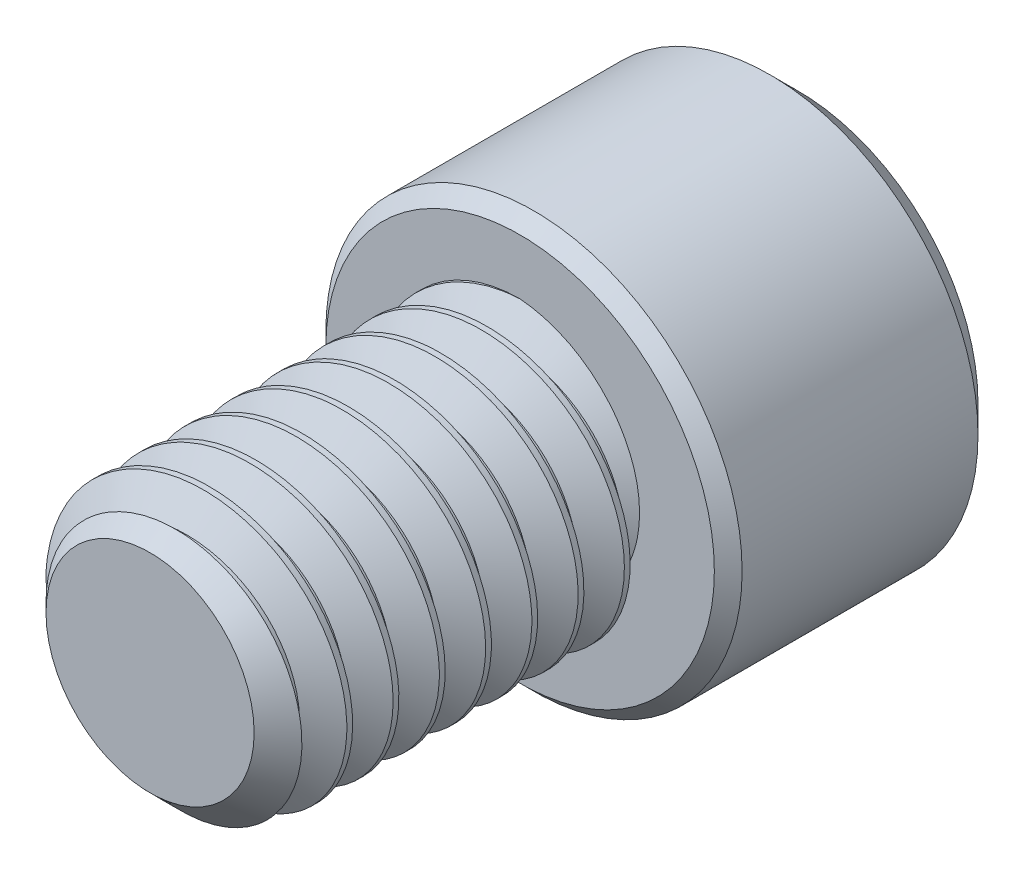
SolidWorks part; units mm, degrees
ref_plane "Front Plane" through (0, 0, 0) normal (0, 0, 1) x (1, 0, 0)
ref_plane "Top Plane" through (0, 0, 0) normal (0, 1, 0) x (1, 0, 0)
ref_plane "Right Plane" through (0, 0, 0) normal (1, 0, 0) x (0, 0, -1)
sketch "Sketch1" plane through (0, 0, 0) normal (0, 0, 1) x (1, 0, 0)
  line L0 (0, 4.7625) -> (0, -4.7625) construction
  circle A0 centre (0, 0) radius 4.7625
  dimension "OD" = 9.525
extrude "Extrude1" add sketch "Sketch1" against normal blind 12.7
sketch "Sketch2" plane through (0, 0, 0) normal (0, 0, 1) x (1, 0, 0)
  circle A0 centre (0, 0) radius 4.7625 construction
  circle A1 centre (0, 0) radius 4.7625
curve "Helix/Spiral1" pitch 1.5875 height 14.2875 turns 9 parameters "pitch"=1.5875
chamfer "Chamfer3" distance 1.1906 angle 45 1 edges at (4.7625, 0, 0)
sketch "Sketch3" plane through (0, 0, 0) normal (1, 0, 0) x (0, 0, -1)
  line L0 (-1.3891, 4.7625) -> (-0.7938, 3.7314)
  line L1 (-0.7938, 3.7314) -> (-0.5953, 3.7314)
  line L2 (-0.5953, 3.7314) -> (0, 4.7625)
  line L3 (-1.3891, 4.7625) -> (0, 4.7625)
  line L4 (-0.6945, 4.7625) -> (-0.6945, 3.7314) construction
  line L5 (-1.0914, 4.2469) -> (-0.2977, 4.2469) construction
  line L6 (0, 4.7625) -> (0, -4.7625) construction
  dimension "D1" = 0.1984
  dimension "D2" = 0.7937
  dimension "D3" = 60
sweep "Cut-Sweep1" cut profiles "Sketch3" path "Helix/Spiral1"
sketch "Sketch6" plane through (0, 0, -12.7) normal (0, 0, -1) x (-1, 0, 0)
  circle A0 centre (0, 0) radius 7.1438
  dimension "head dia" = 14.2875
extrude "Extrude2" add sketch "Sketch6" along normal blind 9.525
sketch "Sketch7" plane through (0, 0, -22.225) normal (0, 0, -1) x (-1, 0, 0)
  line L1 (0, 4.5827) -> (-3.9688, 2.2914)
  line L2 (-3.9688, 2.2914) -> (-3.9688, -2.2914)
  line L3 (-3.9688, -2.2914) -> (0, -4.5827)
  line L4 (0, -4.5827) -> (3.9688, -2.2914)
  line L5 (3.9688, -2.2914) -> (3.9687, 2.2914)
  line L6 (3.9687, 2.2914) -> (0, 4.5827)
  circle A0 centre (0, 0) radius 3.9688 construction
  dimension "hex dia" = 7.9375
extrude "Cut-Extrude1" cut sketch "Sketch7" against normal blind 5.9531
sketch "Sketch8" plane through (0, 0, -22.225) normal (0, 0, -1) x (-1, 0, 0)
  circle A0 centre (0, 0) radius 4.5827
extrude "Cut-Extrude2" cut sketch "Sketch8" against normal blind 0.9525 draft 45
chamfer "Chamfer1" distance 0.9525 angle 45 1 edges at (-7.1438, 0, -22.225)
chamfer "Chamfer2" distance 0.4763 angle 45 1 edges at (-7.1438, 0, -12.7)
sketch "Sketch9" plane through (0, 0, 0) normal (1, 0, 0) x (0, 0, -1)
  line L0 (0, 4.7625) -> (0, -4.7625) construction
  line L1 (8.7313, 4.7625) -> (8.7313, -4.7625) construction
  line L2 (12.7, 7.1437) -> (12.7, -7.1438) construction
  line L3 (22.225, 7.1437) -> (22.225, -7.1438) construction
  line L4 (22.225, 0) -> (0, 0) construction
  dimension "D3" = 14.2875
  dimension "D1" = 8.7312
  dimension "D2" = 9.525
  dimension "D4" = 12.7
equation "\"D3@Helix/Spiral1\" = \"screw length@Extrude1\"+\"pitch@Helix/Spiral1\""
equation "\"D1@Sketch3\" = \"pitch@Helix/Spiral1\"*.125"
equation "\"D2@Sketch3\" = \"pitch@Helix/Spiral1\"*.5"
equation "\"D1@Cut-Extrude1\" = \"hex dia@Sketch7\"*.75"
equation "\"D1@Chamfer1\" = \"head depth@Extrude2\"/10"
equation "\"D1@Sketch9\" = \"pitch@Helix/Spiral1\"*5.5"
equation "\"D1@Chamfer2\" = \"D1@Chamfer1\"/2"
equation "\"D1@Cut-Extrude2\" = \"D1@Chamfer2\"*2"
equation "\"D1@Chamfer3\" = \"pitch@Helix/Spiral1\"*.750"
equation "\"D2@Sketch9\" = \"head depth@Extrude2\""
equation "\"D3@Sketch9\" = \"head dia@Sketch6\""
equation "\"D4@Sketch9\" = \"screw length@Extrude1\""
